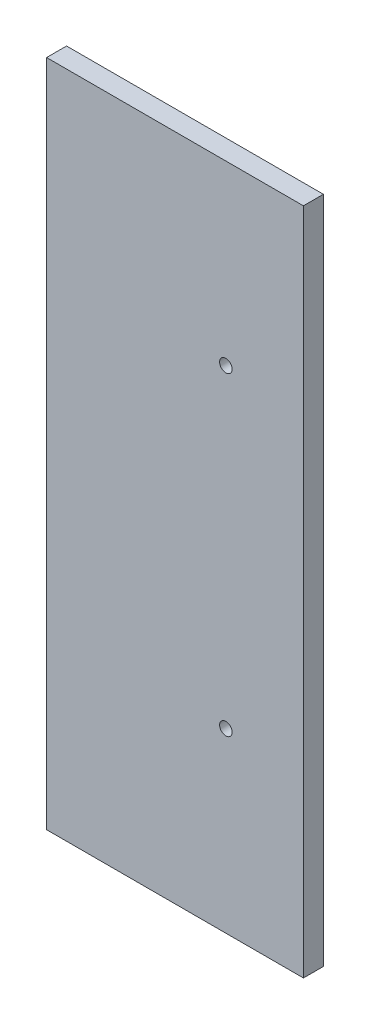
SolidWorks part; units mm, degrees
ref_plane "Front Plane" through (0, 0, 0) normal (0, 0, 1) x (1, 0, 0)
ref_plane "Top Plane" through (0, 0, 0) normal (0, 1, 0) x (1, 0, 0)
ref_plane "Right Plane" through (0, 0, 0) normal (1, 0, 0) x (0, 0, -1)
sketch "Sketch1" plane through (0, 0, 0) normal (0, 0, 1) x (1, 0, 0)
  line L1 (-245.05, 0) -> (0, 0)
  line L2 (-245.05, 0) -> (-245.05, -638.1)
  line L3 (-245.05, -638.1) -> (0, -638.1)
  line L4 (0, 0) -> (0, -638.1)
  dimension "D1" = 638.1
  dimension "D2" = 245.05
extrude "Boss-Extrude1" add sketch "Sketch1" along normal blind 19.05
hole_wizard "Ø12.0mm Dowel Hole1" positions "Sketch2" profile "Sketch3" hole size "Ø12.0" standard "ANSI Metric"
sketch "Sketch2" plane through (0, 0, 0) normal (0, 0, -1) x (-1, 0, 0)
  point P0 (74, -469.05)
  point P3 (74, -169.05)
sketch "Sketch3" plane through (-74, -469.05, 0) normal (1, 0, 0) x (0, 1, 0)
  line L0 (0, 0) -> (0, 30)
  line L1 (0, 30) -> (6, 26.3948)
  line L2 (6, 26.3948) -> (6, 0)
  line L5 (6, 0) -> (0, 0)
  line L10 (0, 30) -> (-6, 26.3948) construction
  line L11 (0, -6.35) -> (0, 107.95) construction
  dimension "Hole Dia." = 12
  dimension "Hole Depth" = 30
  dimension "Drill Angle" = 118
